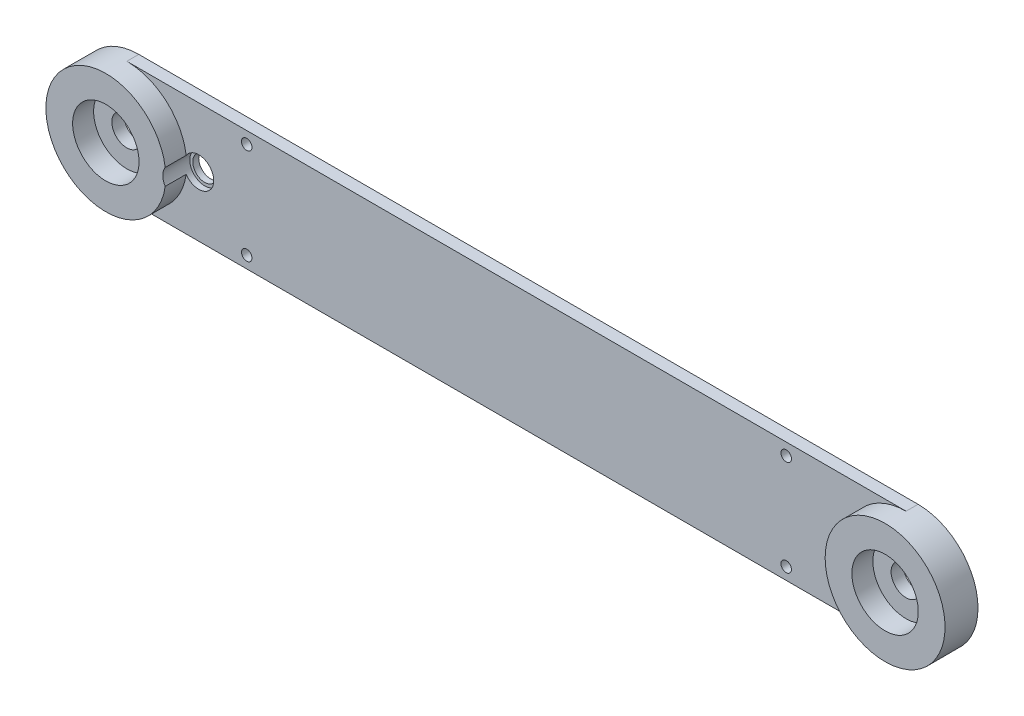
SolidWorks part; units mm, degrees
ref_plane "Ebene vorne" through (0, 0, 0) normal (0, 0, 1) x (1, 0, 0)
ref_plane "Ebene oben" through (0, 0, 0) normal (0, 1, 0) x (1, 0, 0)
ref_plane "Ebene rechts" through (0, 0, 0) normal (1, 0, 0) x (0, 0, -1)
sketch "Skizze1" plane through (0, 0, 0) normal (0, 0, 1) x (1, 0, 0)
  line L0 (-130, 0) -> (0, 0) construction
  line L1 (-130, -20) -> (130, -20)
  line L2 (-130, -20) -> (-130, 20) construction
  line L3 (-130, 20) -> (130, 20)
  line L4 (130, -20) -> (130, 20) construction
  line L5 (-130, -20) -> (130, 20) construction
  line L6 (-130, 20) -> (130, -20) construction
  line L7 (0, 0) -> (130, 0) construction
  arc A0 (-130, 20) -> (-130, -20) centre (-130, 0) ccw
  arc A1 (130, 20) -> (130, -20) centre (130, 0) cw
  point P0 (0, 0)
  dimension "D1" = 260
  dimension "D2" = 40
extrude "Aufsatz-Linear austragen1" add sketch "Skizze1" along normal blind 4
sketch "Skizze2" plane through (0, 0, 4) normal (0, 0, 1) x (1, 0, 0)
  circle A0 centre (-130, 0) radius 20
  circle A1 centre (-130, 0) radius 11.075
  dimension "D1" = 22.15
extrude "Aufsatz-Linear austragen2" add sketch "Skizze2" along normal blind 7
sketch "Skizze3" plane through (0, 0, 4) normal (0, 0, 1) x (1, 0, 0)
  circle A0 centre (-130, 0) radius 5
  dimension "D1" = 10
extrude "Schnitt-Linear austragen1" cut sketch "Skizze3" against normal through all and the other way through all
mirror "Spiegeln1" about plane through (0, 0, 0) normal (1, 0, 0) of "Aufsatz-Linear austragen2", "Schnitt-Linear austragen1"
sketch "Skizze4" plane through (0, 0, 4) normal (0, 0, 1) x (1, 0, 0)
  line L0 (-130, 20) -> (130, 20) construction
  line L1 (0, 0) -> (-130, 0) construction
  line L2 (0, 0) -> (0, 20) construction
  circle A0 centre (-130, 0) radius 30 construction
  circle A1 centre (-90, 16) radius 4 construction
  circle A2 centre (-90, 16) radius 1.75
  circle A3 centre (-90, -16) radius 4 construction
  circle A4 centre (-90, -16) radius 1.75
  circle A5 centre (90, -16) radius 4 construction
  circle A6 centre (90, 16) radius 4 construction
  circle A7 centre (90, -16) radius 1.75
  circle A8 centre (90, 16) radius 1.75
  dimension "D1" = 60
  dimension "D2" = 8
  dimension "D3" = 3.5
  dimension "D4" = 40
extrude "Schnitt-Linear austragen2" cut sketch "Skizze4" against normal through all
sketch "Skizze5" plane through (0, 0, 0) normal (0, 0, -1) x (-1, 0, 0)
  line L0 (130, 0) -> (106, 0) construction
  circle A0 centre (106, 0) radius 4
  dimension "D1" = 8
  dimension "D2" = 24
extrude "Schnitt-Linear austragen3" cut sketch "Skizze5" against normal through all
sketch "Skizze6" plane through (0, 0, 4) normal (0, 0, 1) x (1, 0, 0)
  circle A0 centre (-106, 0) radius 5
  dimension "D1" = 10
extrude "Schnitt-Linear austragen4" cut sketch "Skizze6" against normal blind 2 and the other way through all
